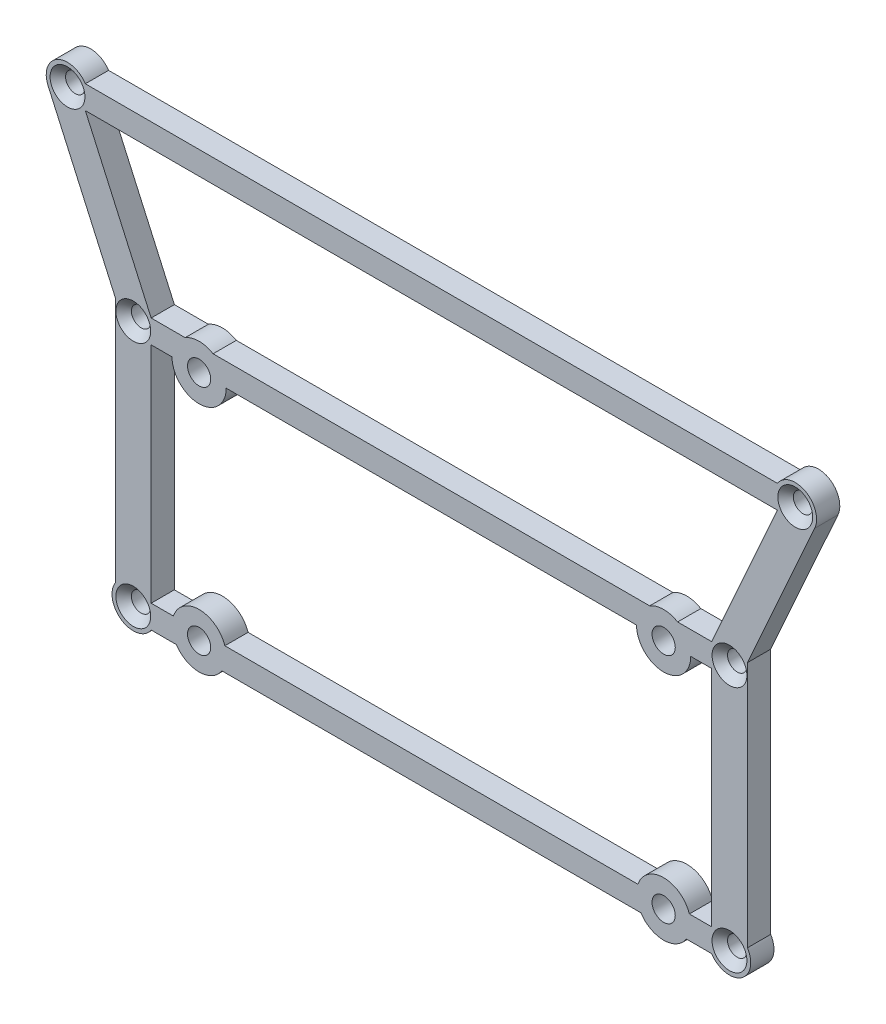
SolidWorks part; units mm, degrees
ref_plane "Front Plane" through (0, 0, 0) normal (0, 0, 1) x (1, 0, 0)
ref_plane "Top Plane" through (0, 0, 0) normal (0, 1, 0) x (1, 0, 0)
ref_plane "Right Plane" through (0, 0, 0) normal (1, 0, 0) x (0, 0, -1)
sketch "Sketch1" plane through (0, 0, 0) normal (0, 0, 1) x (1, 0, 0)
  line L0 (8.5, 31.9015) -> (85.5, 31.9015) construction
  line L1 (0, 0) -> (94, 0) construction
  line L2 (0, 0) -> (0, 53.8533) construction
  line L3 (0, 53.8533) -> (94, 53.8533) construction
  line L5 (94, 53.8533) -> (85.5, 0) construction
  line L6 (94, 53.8533) -> (85.5, 31.9015) construction
  line L7 (8.5, 31.9015) -> (8.5, 0) construction
  line L8 (8.5, 0) -> (85.5, 0) construction
  line L9 (85.5, 31.9015) -> (85.5, 0) construction
  line L10 (47, 55.3533) -> (47, -1.5) construction
  line L11 (0, 53.8533) -> (8.5, 31.9015) construction
  line L12 (0, 53.8533) -> (8.5, 0) construction
  line L14 (6.1738, 33.3682) -> (-2.5092, 52.7279)
  line L15 (2.3049, 55.3533) -> (91.6951, 55.3533)
  line L16 (10.8049, 33.4015) -> (2.3049, 52.3533)
  line L17 (10.8049, 33.4015) -> (83.1951, 33.4015)
  line L18 (10.8049, 30.4015) -> (83.1951, 30.4015)
  line L19 (10.8049, 30.4015) -> (10.8049, 1.5)
  line L20 (10.8049, 1.5) -> (83.1951, 1.5)
  line L21 (10.8049, -1.5) -> (83.1951, -1.5)
  line L22 (2.3049, 52.3533) -> (91.6951, 52.3533)
  line L23 (6.1738, 1.4667) -> (6.1738, 33.3682)
  line L24 (94, 0) -> (94, 53.8533) construction
  line L25 (87.8262, 1.4667) -> (87.8262, 33.3682)
  line L26 (83.1951, 30.4015) -> (83.1951, 1.5)
  line L27 (83.1951, 33.4015) -> (91.6951, 52.3533)
  line L28 (87.8262, 33.3682) -> (96.5092, 52.7279)
  circle A0 centre (0, 53.8533) radius 1.25
  circle A2 centre (8.5, 31.9015) radius 1.25
  circle A4 centre (8.5, 0) radius 1.25
  arc A9 (6.1738, 1.4667) -> (10.8049, -1.5) centre (8.5, 0) ccw
  arc A10 (2.3049, 55.3533) -> (-2.5092, 52.7279) centre (0, 53.8533) ccw
  circle A11 centre (8.5, 0) radius 2.75 construction
  circle A12 centre (8.5, 31.9015) radius 2.75 construction
  circle A13 centre (0, 53.8533) radius 2.75 construction
  circle A14 centre (94, 53.8533) radius 2.75 construction
  circle A15 centre (85.5, 31.9015) radius 2.75 construction
  circle A16 centre (85.5, 0) radius 2.75 construction
  arc A17 (91.6951, 55.3533) -> (96.5092, 52.7279) centre (94, 53.8533) cw
  arc A18 (87.8262, 1.4667) -> (83.1951, -1.5) centre (85.5, 0) cw
  circle A19 centre (85.5, 0) radius 1.25
  circle A20 centre (85.5, 31.9015) radius 1.25
  circle A21 centre (94, 53.8533) radius 1.25
  point P9 (47, 53.8533)
  point P28 (47, 0)
  point P29 (47, 31.9015)
  point P37 (47, 55.2859)
  point P47 (47, 52.3533)
  point P50 (47, 1.5)
  point P51 (47, 1.5)
  point P53 (47, 30.4015)
  point P55 (47, 33.4015)
  point P58 (47, 30.5)
  point P59 (47, 33.5)
  point P60 (47, 52.2859)
  dimension "D7" = 2.5
  dimension "D9" = 5.5
  dimension "D16" = 2.75
  dimension "D2" = 38.5
  dimension "D3" = 47
  dimension "D4" = 56.8533
  dimension "D5" = 23.54
  dimension "D6" = 54.52
  dimension "D10" = 3
  dimension "D11" = 3
  dimension "D12" = 3
  dimension "D13" = 1.5
  dimension "D14" = 1.5
  dimension "D15" = 1.5
  dimension "D17" = 1.1254
extrude "Boss-Extrude1" add sketch "Sketch1" along normal blind 3
chamfer "Chamfer1" distance 1 angle 45 6 edges at (9.75, 0, 3) (9.75, 31.9015, 3) (1.25, 53.8533, 3) (92.75, 53.8533, 3) (84.25, 31.9015, 3) (84.25, 0, 3)
sketch "Sketch2" plane through (0, 0, 3) normal (0, 0, 1) x (1, 0, 0)
  line L0 (47, 55.3533) -> (47, -1.5) construction
  line L1 (17, 30.4015) -> (77, 30.4015) construction
  line L2 (17, 30.4015) -> (17, 0.4015) construction
  line L3 (17, 0.4015) -> (77, 0.4015) construction
  line L4 (77, 30.4015) -> (77, 0.4015) construction
  line L5 (17, 30.4015) -> (77, 0.4015) construction
  line L6 (17, 0.4015) -> (77, 30.4015) construction
  line L7 (10.8049, -1.5) -> (83.1951, -1.5) construction
  line L8 (91.6951, 55.3533) -> (2.3049, 55.3533) construction
  line L9 (83.1951, 30.4015) -> (10.8049, 30.4015) construction
  circle A0 centre (17, 30.4015) radius 3.5
  circle A1 centre (17, 0.4015) radius 3.5
  circle A2 centre (17, 0.4015) radius 1.5
  circle A3 centre (17, 30.4015) radius 1.5
  circle A4 centre (77, 30.4015) radius 1.5
  circle A5 centre (77, 30.4015) radius 3.5
  circle A6 centre (77, 0.4015) radius 1.5
  circle A7 centre (77, 0.4015) radius 3.5
  point P19 (47, 30.4015)
  line M16 (83.1951, 1.5) -> (10.8049, 1.5)
  line M18 (10.8049, 30.4015) -> (83.1951, 30.4015)
  dimension "D2" = 3
  dimension "D3" = 7
  dimension "D4" = 60
  dimension "D5" = 30
  dimension "D1" = 0
extrude "Boss-Extrude2" add sketch "Sketch2" against normal up to surface (3 mm away) contours A1 | A7 | A0 | A5 up to face at (47, 42.8774, 0)
extrude "Cut-Extrude1" cut sketch "Sketch2<3>" against normal blind 3 contours A2 M16 | A2 M16 | A3 M18 | A3 M18 | A4 M18 | A4 M18 | A6 M16 | A6 M16 region at (17, 31.0381, 3) region at (17, 29.7649, 3) region at (77, 29.7649, 3) region at (77, 31.0381, 3) region at (17, 1.6626, 3) region at (17, 0.2923, 3) region at (77, 0.2923, 3) region at (77, 1.6626, 3)
sketch "Sketch2<3>" plane through (0, 0, 3) normal (0, 0, 1) x (1, 0, 0) same geometry as "Sketch2"
